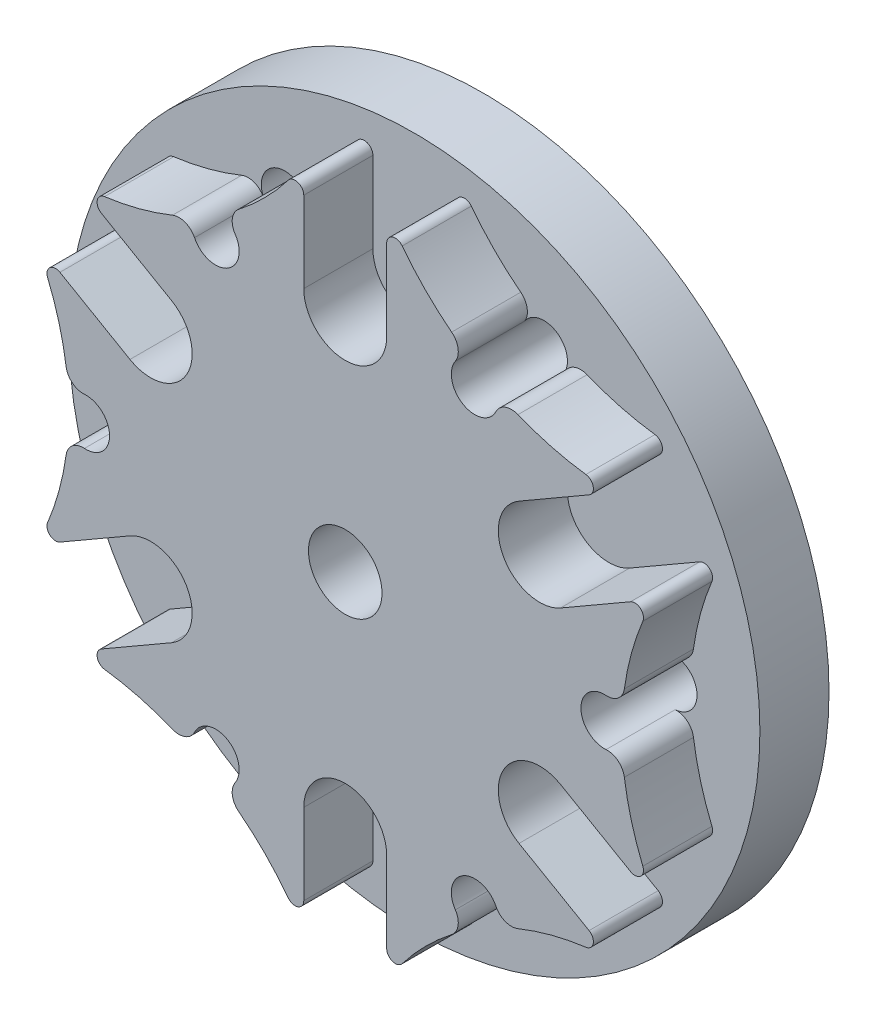
SolidWorks part; units mm, degrees
ref_plane "Front Plane" through (0, 0, 0) normal (0, 0, 1) x (1, 0, 0)
ref_plane "Top Plane" through (0, 0, 0) normal (0, 1, 0) x (1, 0, 0)
ref_plane "Right Plane" through (0, 0, 0) normal (1, 0, 0) x (0, 0, -1)
sketch "Sketch2" plane through (0, 0, 0) normal (0, 0, 1) x (1, 0, 0)
  circle A0 centre (0, 0) radius 31.75
  point P17 (0, 0)
  dimension "D4" = 63.5
extrude "Boss-Extrude1" add sketch "Sketch2" along normal blind 6.35
sketch "Sketch3" plane through (0, 0, 6.35) normal (0, 0, 1) x (1, 0, 0)
  line L0 (0, 30.6138) -> (0, 20.6375) construction
  line L1 (3.81, 30.6138) -> (3.81, 20.6375)
  line L2 (-3.81, 30.6138) -> (-3.81, 20.6375)
  line L5 (24.6073, 18.6065) -> (15.9676, 13.6183)
  line L8 (28.4173, 12.0073) -> (19.7776, 7.0192)
  line L11 (26.5123, 15.3069) -> (17.8726, 10.3187) construction
  line L14 (28.4173, -12.0073) -> (19.7776, -7.0192)
  line L17 (24.6073, -18.6065) -> (15.9676, -13.6183)
  line L18 (26.5123, -15.3069) -> (17.8726, -10.3187) construction
  line L19 (3.81, -30.6138) -> (3.81, -20.6375)
  line L20 (-3.81, -30.6138) -> (-3.81, -20.6375)
  line L21 (0, -30.6138) -> (0, -20.6375) construction
  line L22 (-24.6073, -18.6065) -> (-15.9676, -13.6183)
  line L23 (-28.4173, -12.0073) -> (-19.7776, -7.0192)
  line L24 (-26.5123, -15.3069) -> (-17.8726, -10.3188) construction
  line L25 (-28.4173, 12.0073) -> (-19.7776, 7.0192)
  line L26 (-24.6073, 18.6065) -> (-15.9676, 13.6183)
  line L27 (-26.5123, 15.3069) -> (-17.8726, 10.3187) construction
  circle A0 centre (0, 0) radius 20.6375 construction
  arc A1 (3.81, 30.6138) -> (-3.81, 30.6138) centre (0, 30.6138) ccw
  arc A2 (-3.81, 20.6375) -> (3.81, 20.6375) centre (0, 20.6375) ccw
  arc A13 (-3.81, 30.6138) -> (-24.6073, 18.6065) centre (-25.4, 43.9941) cw
  arc A14 (28.4173, 12.0073) -> (24.6073, 18.6065) centre (26.5123, 15.3069) ccw
  arc A15 (15.9676, 13.6183) -> (19.7776, 7.0192) centre (17.8726, 10.3187) ccw
  arc A16 (24.6073, -18.6065) -> (28.4173, -12.0073) centre (26.5123, -15.3069) ccw
  arc A17 (19.7776, -7.0192) -> (15.9676, -13.6183) centre (17.8726, -10.3187) ccw
  arc A18 (-3.81, -30.6138) -> (3.81, -30.6138) centre (0, -30.6138) ccw
  arc A19 (3.81, -20.6375) -> (-3.81, -20.6375) centre (0, -20.6375) ccw
  arc A20 (-28.4173, -12.0073) -> (-24.6073, -18.6065) centre (-26.5123, -15.3069) ccw
  arc A21 (-15.9676, -13.6183) -> (-19.7776, -7.0192) centre (-17.8726, -10.3188) ccw
  arc A22 (-24.6073, 18.6065) -> (-28.4173, 12.0073) centre (-26.5123, 15.3069) ccw
  arc A23 (-19.7776, 7.0192) -> (-15.9676, 13.6183) centre (-17.8726, 10.3187) ccw
  arc A24 (24.6073, 18.6065) -> (3.81, 30.6138) centre (25.4, 43.9941) cw
  arc A25 (28.4173, -12.0073) -> (28.4173, 12.0073) centre (50.8, 0) cw
  arc A26 (3.81, -30.6138) -> (24.6073, -18.6065) centre (25.4, -43.9941) cw
  arc A27 (-24.6073, -18.6065) -> (-3.81, -30.6138) centre (-25.4, -43.9941) cw
  arc A28 (-28.4173, 12.0073) -> (-28.4173, -12.0073) centre (-50.8, 0) cw
  point P5 (0, 25.6257)
  point P10 (-12.7, 21.997)
  point P17 (22.1925, 12.8128)
  point P24 (22.1925, -12.8128)
  point P31 (0, -25.6257)
  point P38 (-22.1925, -12.8128)
  point P45 (-22.1925, 12.8128)
  point P51 (0, 0)
  point P67 (0, 0)
  dimension "D1" = 41.275
  dimension "D2" = 3.81
  dimension "D5" = 25.4
  dimension "D3" = 25.4
  dimension "D4" = 6
  dimension "D6" = 6
extrude "Boss-Extrude2" add sketch "Sketch3" along normal blind 6.35
sketch "Sketch4" plane through (0, 0, 12.7) normal (0, 0, 1) x (1, 0, 0)
  circle A0 centre (0, 0) radius 3.3782
  dimension "D1" = 6.7564
extrude "Cut-Extrude1" cut sketch "Sketch4" against normal through all
fillet "Fillet2" radius 0.7937 12 edges at (-24.6073, 18.6065, 9.525) (-3.81, 30.6138, 9.525) (3.81, 30.6138, 9.525) (24.6073, 18.6065, 9.525) (28.4173, 12.0073, 9.525) (28.4173, -12.0073, 9.525) (24.6073, -18.6065, 9.525) (3.81, -30.6138, 9.525) (-3.81, -30.6138, 9.525) (-28.4173, 12.0073, 9.525) (-28.4173, -12.0073, 9.525) (-24.6073, -18.6065, 9.525)
sketch "Sketch5" plane through (0, 0, 0) normal (0, 0, -1) x (-1, 0, 0)
  line L0 (-1.0086, 1.747) -> (-22704.1831, 39324.7986) construction
  line L1 (0, 1.3224) -> (0, 50001.3224) construction
  circle A0 centre (0, 0) radius 23.8125 construction
  circle A1 centre (-11.9063, 20.6222) radius 2.159
  circle A2 centre (11.9063, 20.6222) radius 2.159
  circle A3 centre (23.8125, 0) radius 2.159
  circle A4 centre (11.9063, -20.6222) radius 2.159
  circle A5 centre (-11.9062, -20.6222) radius 2.159
  circle A6 centre (-23.8125, 0) radius 2.159
  point P17 (0, 0)
  dimension "D1" = 47.625
  dimension "D2" = 4.318
  dimension "D4" = 30
  dimension "D3" = 6
extrude "Cut-Extrude2" cut sketch "Sketch5" against normal through all
fillet "Fillet3" radius 1.5875 12 edges at (25.4397, -1.419, 9.525) (25.4397, 1.419, 9.525) (13.9487, 21.3219, 9.525) (11.4909, 22.7409, 9.525) (-11.4909, 22.7409, 9.525) (-13.9487, 21.3219, 9.525) (-25.4397, 1.419, 9.525) (-25.4397, -1.419, 9.525) (-13.9487, -21.3219, 9.525) (-11.4909, -22.7409, 9.525) (11.4909, -22.7409, 9.525) (13.9487, -21.3219, 9.525)
